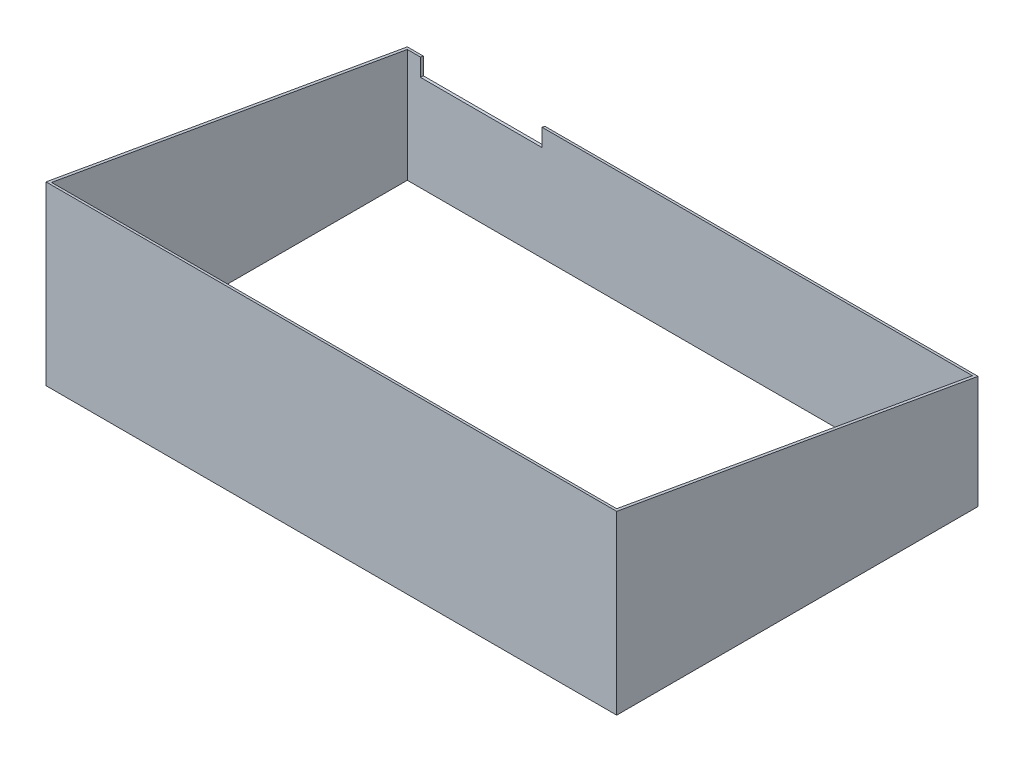
SolidWorks part; units mm, degrees
ref_plane "Front Plane" through (0, 0, 0) normal (0, 0, 1) x (1, 0, 0)
ref_plane "Top Plane" through (0, 0, 0) normal (0, 1, 0) x (1, 0, 0)
ref_plane "Right Plane" through (0, 0, 0) normal (1, 0, 0) x (0, 0, -1)
sketch "Sketch1" plane through (0, 0, 0) normal (1, 0, 0) x (0, 0, -1)
  line L0 (0, 402.1265) -> (0, 0)
  line L1 (0, 0) -> (823.0531, 0)
  line L4 (823.0531, 0) -> (823.0531, 257)
  line L5 (0, 402.1265) -> (823.0531, 257)
  dimension "D1" = 10
  dimension "D2" = 835.75
  dimension "D3" = 257
extrude "Boss-Extrude1" add sketch "Sketch1" along normal blind 1300
shell "Shell1" thickness 6.35 removed face at (650, 0, -411.5265) removed face at (650, 329.5632, -411.5265)
sketch "Sketch3" plane through (0, 0, -816.7031) normal (0, 0, 1) x (1, 0, 0)
  line L0 (6.35, 0) -> (6.35, 258.1197) construction
  line L1 (36.35, 268.1197) -> (313.35, 268.1197)
  line L2 (36.35, 268.1197) -> (36.35, 218.1197)
  line L3 (36.35, 218.1197) -> (313.35, 218.1197)
  line L4 (313.35, 268.1197) -> (313.35, 218.1197)
  line L5 (1293.65, 258.1197) -> (6.35, 258.1197) construction
  dimension "D1" = 30
  dimension "D2" = 277
  dimension "D3" = 10
  dimension "D4" = 40
extrude "Cut-Extrude2" cut sketch "Sketch3" against normal up to next
